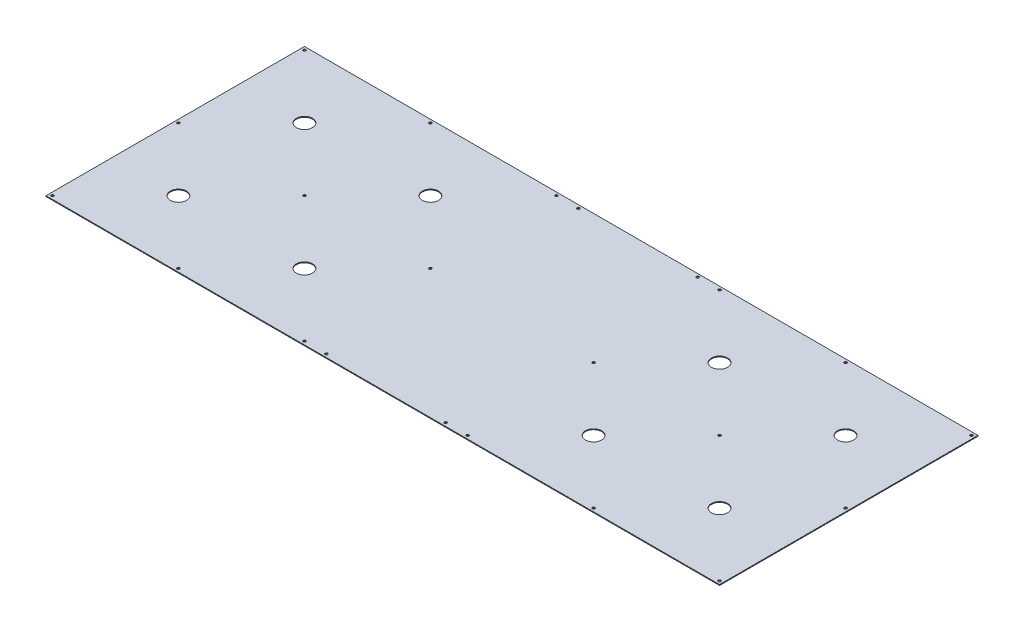
SolidWorks part; units mm, degrees
ref_plane "Front Plane" through (0, 0, 0) normal (0, 0, 1) x (1, 0, 0)
ref_plane "Top Plane" through (0, 0, 0) normal (0, 1, 0) x (1, 0, 0)
ref_plane "Right Plane" through (0, 0, 0) normal (1, 0, 0) x (0, 0, -1)
sketch "main_plate" plane through (0, 0, 0) normal (0, 1, 0) x (1, 0, 0)
  line L1 (-417, 160) -> (417, 160)
  line L2 (-417, 160) -> (-417, -160)
  line L3 (-417, -160) -> (417, -160)
  line L4 (417, 160) -> (417, -160)
  line L5 (-417, 160) -> (417, -160) construction
  line L6 (-417, -160) -> (417, 160) construction
  point P0 (0, 0)
  dimension "D1" = 320
  dimension "D2" = 834
extrude "Boss-Extrude1" add sketch "main_plate" along normal blind 1.016
sketch "main_holes" plane through (0, 1.016, 0) normal (0, 1, 0) x (1, 0, 0)
  line L0 (-417, 160) -> (-417, -160) construction
  line L1 (417, 160) -> (-417, 160) construction
  line L2 (-417, 0) -> (417, 0) construction
  line L3 (417, -160) -> (417, 160) construction
  line L4 (-417, -160) -> (417, -160) construction
  line L5 (0, 160) -> (0, -160) construction
  circle A0 centre (-413, 156) radius 1.6
  circle A6 centre (-257, 156) radius 1.6
  circle A7 centre (-101, 156) radius 1.6
  circle A8 centre (-257, 0) radius 1.6
  circle A9 centre (-101, 0) radius 1.6
  circle A10 centre (-257, -156) radius 1.6
  circle A11 centre (-101, -156) radius 1.6
  circle A12 centre (-413, 0) radius 1.6
  circle A13 centre (-413, -156) radius 1.6
  circle A18 centre (413, -156) radius 1.6
  circle A19 centre (413, 0) radius 1.6
  circle A20 centre (101, -156) radius 1.6
  circle A21 centre (257, -156) radius 1.6
  circle A22 centre (101, 0) radius 1.6
  circle A23 centre (257, 0) radius 1.6
  circle A24 centre (101, 156) radius 1.6
  circle A25 centre (257, 156) radius 1.6
  circle A28 centre (413, 156) radius 1.6
  circle A29 centre (-73.8188, 156) radius 1.6
  circle A31 centre (73.8188, 156) radius 1.6
  circle A32 centre (73.8188, -156) radius 1.6
  circle A33 centre (-73.8188, -156) radius 1.6
  point P8 (-52.1362, 156)
  point P19 (45.2632, 156)
  dimension "D3" = 3.2
  dimension "D1" = 4
  dimension "D2" = 4
  dimension "D4" = 3
  dimension "D5" = 3
  dimension "D6" = 73.8188
extrude "Cut-Extrude1" cut sketch "main_holes" against normal through all
sketch "sma" plane through (0, 1.016, 0) normal (0, 1, 0) x (1, 0, 0)
  line L0 (0, 160) -> (0, -160) construction
  line L1 (417, 160) -> (-417, 160) construction
  line L2 (-417, -160) -> (417, -160) construction
  line L3 (-413, 156) -> (-257, 156) construction
  line L7 (-257, 0) -> (-413, 0) construction
  line L8 (-413, 0) -> (-413, 156) construction
  line L9 (-257, 156) -> (-257, 0) construction
  circle A0 centre (-335, 78) radius 10
  circle A1 centre (-179, 78) radius 10
  circle A2 centre (-179, -78) radius 10
  circle A3 centre (-335, -78) radius 10
  circle A4 centre (335, 78) radius 10
  circle A5 centre (179, 78) radius 10
  circle A6 centre (335, -78) radius 10
  circle A7 centre (179, -78) radius 10
  point P9 (-413, 78)
  point P10 (-335, 156)
  dimension "D1" = 20
  dimension "D2" = 2
  dimension "D3" = 2
extrude "Cut-Extrude2" cut sketch "sma" against normal through all
